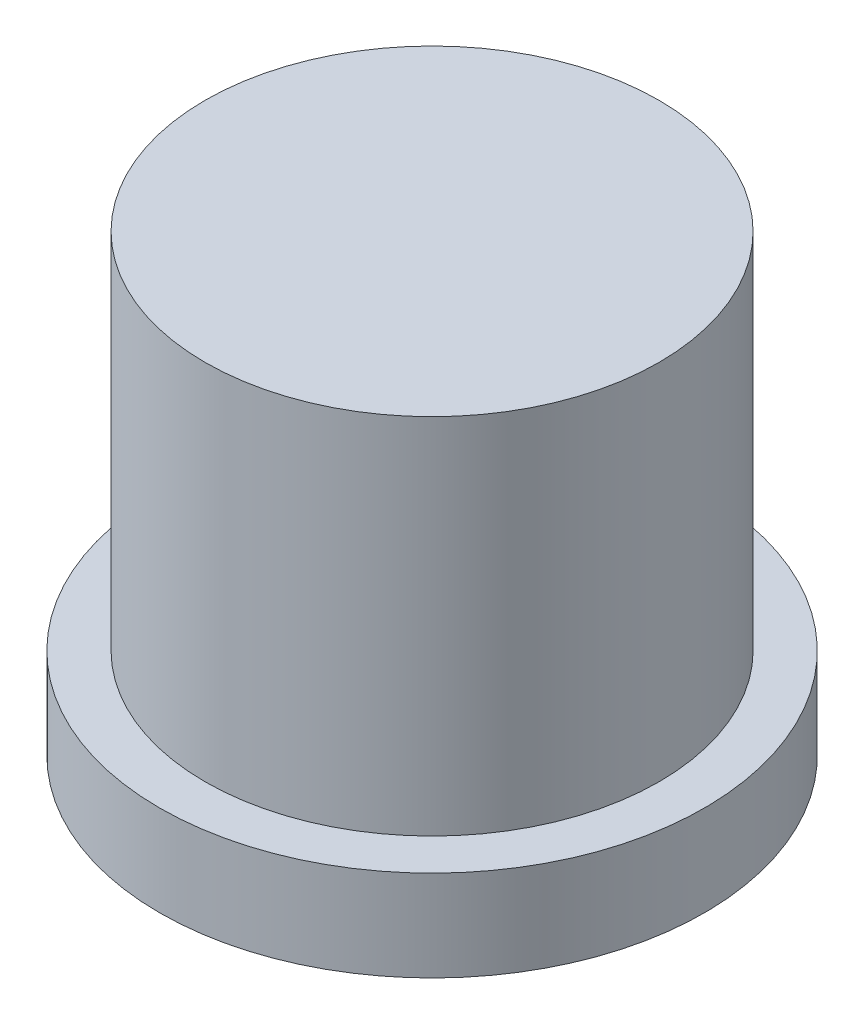
SolidWorks part; units mm, degrees
ref_plane "Front Plane" through (0, 0, 0) normal (0, 0, 1) x (1, 0, 0)
ref_plane "Top Plane" through (0, 0, 0) normal (0, 1, 0) x (1, 0, 0)
ref_plane "Right Plane" through (0, 0, 0) normal (1, 0, 0) x (0, 0, -1)
sketch "Sketch1" plane through (0, 0, 0) normal (0, 1, 0) x (1, 0, 0)
  circle A0 centre (0, 0) radius 5
  circle A1 centre (0, 0) radius 6
  dimension "D1" = 10
  dimension "D2" = 1
extrude "Boss-Extrude1" add sketch "Sketch1" along normal blind 10 contours A0
extrude "Boss-Extrude2" add sketch "Sketch1<3>" along normal blind 2
sketch "Sketch1<3>" plane through (0, 0, 0) normal (0, 1, 0) x (1, 0, 0) same geometry as "Sketch1"
